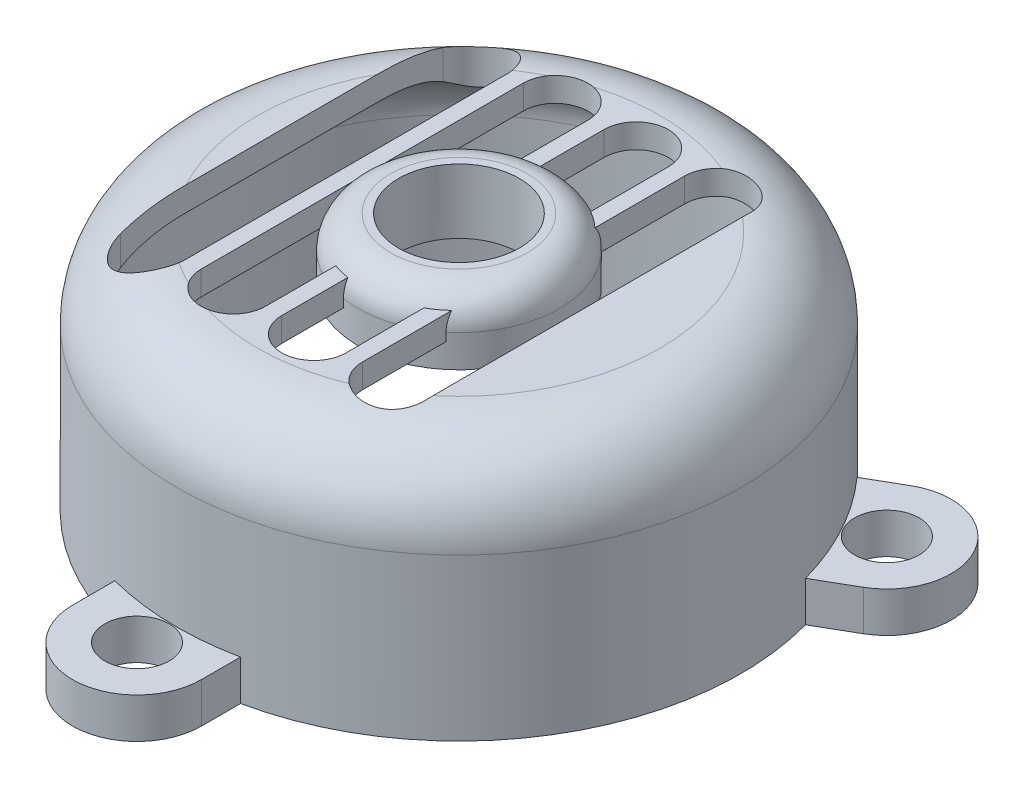
SolidWorks part; units mm, degrees
ref_plane "Front Plane" through (0, 0, 0) normal (0, 0, 1) x (1, 0, 0)
ref_plane "Top Plane" through (0, 0, 0) normal (0, 1, 0) x (1, 0, 0)
ref_plane "Right Plane" through (0, 0, 0) normal (1, 0, 0) x (0, 0, -1)
sketch "Sketch1" plane through (0, 0, 0) normal (0, 1, 0) x (1, 0, 0)
  circle A0 centre (0, 0) radius 35
  dimension "D1" = 70
extrude "Boss-Extrude1" add sketch "Sketch1" along normal blind 30
fillet "Fillet1" radius 10 1 edges at (0, 30, 35)
shell "Shell1" thickness 3 removed face at (0, 0, 35)
sketch "Sketch3" plane through (0, 0, 0) normal (0, -1, 0) x (1, 0, 0)
  line L1 (-8.8504, 32) -> (7.1496, 32)
  line L2 (-8.8504, 32) -> (-8.8504, 39.1167)
  line L3 (-8.8504, 39.1167) -> (7.1496, 39.1167) construction
  line L4 (7.1496, 32) -> (7.1496, 39.1167)
  line L5 (-8.8504, 32) -> (7.1496, 39.1167) construction
  line L6 (-8.8504, 39.1167) -> (7.1496, 32) construction
  arc A0 (7.1496, 39.1167) -> (-8.8504, 39.1167) centre (-0.8504, 39.1167) ccw
  circle A1 centre (-0.8504, 39.1167) radius 4
  circle A2 centre (0, 0) radius 32 construction
  point P0 (-0.8504, 35.5583)
  dimension "D1" = 8
  dimension "D2" = 8
extrude "Boss-Extrude3" add sketch "Sketch3" against normal blind 5
pattern_circular "CirPattern2" count 3 over 360 about axis through (0, 0, 0) along (0, 1, 0) of "Boss-Extrude3"
sketch "Sketch4" plane through (0, 30, 0) normal (0, 1, 0) x (1, 0, 0)
  line L0 (-18, 20) -> (-18, -20) construction
  line L1 (-14, 20) -> (-14, -20)
  line L2 (-22, 20) -> (-22, -20)
  line L3 (0, 0) -> (15.1718, 0)
  arc A0 (-14, 20) -> (-22, 20) centre (-18, 20) ccw
  arc A1 (-22, -20) -> (-14, -20) centre (-18, -20) ccw
  point P2 (-18, 0)
  dimension "D1" = 4
  dimension "D2" = 40
  dimension "D3" = 18
extrude "Cut-Extrude1" cut sketch "Sketch4" against normal through all
sketch "Sketch5" plane through (0, 30, 0) normal (0, 1, 0) x (1, 0, 0)
  line L0 (0, 0) -> (14.1416, 0)
pattern_linear "LPattern1" count 4 spacing 10 along (1, 0, 0) of "Cut-Extrude1"
sketch "Sketch6" plane through (0, 27, 0) normal (0, -1, 0) x (1, 0, 0)
  circle A0 centre (0, 0) radius 12.5
  dimension "D1" = 25
extrude "Boss-Extrude4" add sketch "Sketch6" against normal blind 5 and the other way blind 3
fillet "Fillet2" radius 4 1 edges at (0, 32, -12.5)
sketch "Sketch8" plane through (0, 32, 0) normal (0, 1, 0) x (1, 0, 0)
  circle A0 centre (0, 0) radius 7.5
  dimension "D1" = 15
extrude "Cut-Extrude2" cut sketch "Sketch8" against normal through all
